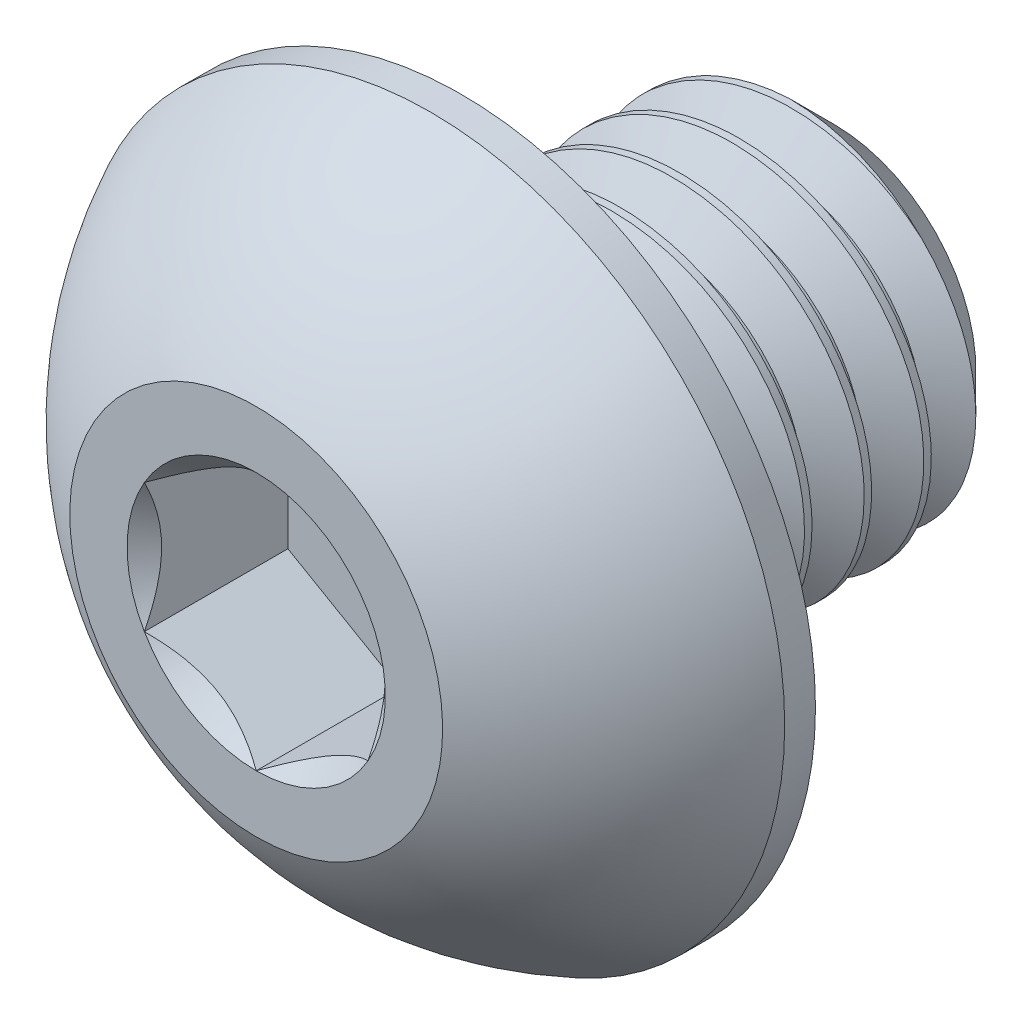
SolidWorks part; units mm, degrees
note: '?' marks a value the reader was unsure of.
ref_plane "Front" through (0, 0, 0) normal (0, 0, 1) x (1, 0, 0)
ref_plane "Top" through (0, 0, 0) normal (0, 1, 0) x (1, 0, 0)
ref_plane "Right" through (0, 0, 0) normal (1, 0, 0) x (0, 0, -1)
sketch "Sketch1" plane through (0, 0, 0) normal (1, 0, 0) x (0, 0, -1)
  line L2 (2.75, 2.5) -> (7.75, 2.5)
  line L3 (7.75, 2.5) -> (7.75, 0)
  line L4 (7.75, 0) -> (2.75, 0)
  line L6 (2.3375, 4.75) -> (2.75, 4.75) construction
  line L7 (7.75, 2.5) -> (7.75, -2.5) construction
  line L8 (0, 0) -> (2.75, 0) construction
  line L9 (2.75, 4.75) -> (2.75, -4.75) construction
  line L11 (2.75, 2.5) -> (2.75, 0)
  line L13 (0, 1.5) -> (0, -1.5) construction
  line L14 (0, 1.5) -> (0, 2.5) construction
  arc A3 (0, 2.5) -> (2.3375, 4.75) centre (4.6581, 0) cw construction
  dimension "D1" = 0.4125
revolve "Revolve1" add sketch "Sketch1" angle 360 mid plane about L4
sketch "Sketch3" plane through (0, 0, -7.75) normal (0, 0, -1) x (-1, 0, 0)
  circle A0 centre (0, 0) radius 2.5
curve "Helix/Spiral1" pitch 0.8 height 5.8 turns 7.25
chamfer "Chamfer1" distance 0.6 angle 45 1 edges at (0, 2.5, -7.75)
sketch "Sketch7" plane through (0, 0, 0) normal (1, 0, 0) x (0, 0, -1)
  line L6 (2.3375, 4.75) -> (2.75, 4.75) construction
  line L8 (0, 0) -> (2.75, 0) construction
  line L11 (2.75, 4.75) -> (2.75, -4.75) construction
  line L12 (2.3375, 4.75) -> (2.75, 4.75)
  line L13 (0, 0) -> (2.75, 0)
  line L14 (0, 1.5) -> (0, -1.5) construction
  line L15 (2.75, 4.75) -> (2.75, 0)
  line L16 (0, 2.5) -> (0, 0)
  arc A2 (2.3375, 4.75) -> (0, 2.5) centre (4.6581, 0) ccw construction
  arc A3 (2.3375, 4.75) -> (0, 2.5) centre (4.6581, 0) ccw
revolve "Revolve2" add sketch "Sketch7" angle 360 mid plane about L13
sketch "Sketch5" plane through (0, 0, 0) normal (0, 0, 1) x (1, 0, 0)
  line L1 (1.5, -0.866) -> (1.5, 0.866)
  line L2 (1.5, 0.866) -> (0, 1.7321)
  line L3 (0, 1.7321) -> (-1.5, 0.866)
  line L4 (-1.5, 0.866) -> (-1.5, -0.866)
  line L5 (-1.5, -0.866) -> (0, -1.7321)
  line L6 (0, -1.7321) -> (1.5, -0.866)
  circle A0 centre (0, 0) radius 1.5 construction
extrude "Cut-Extrude2" cut sketch "Sketch5" against normal blind 1.925
sketch "Sketch6" plane through (0, 0, 0) normal (0, 0, 1) x (1, 0, 0)
  circle A0 centre (0, 0) radius 1.7321
extrude "Cut-Extrude3" cut sketch "Sketch6" against normal blind 1.925 draft 45
sketch "Sketch2" plane through (0, 0, 0) normal (1, 0, 0) x (0, 0, -1)
  line L0 (7.15, 2.5) -> (7.85, 2.5)
  line L1 (7.85, 2.5) -> (7.55, 1.9804)
  line L2 (7.55, 1.9804) -> (7.45, 1.9804)
  line L3 (7.45, 1.9804) -> (7.15, 2.5)
  line L4 (7.3, 2.2402) -> (7.7, 2.2402) construction
  dimension "D1" = 60
  dimension "D2" = 0.1
  dimension "D3" = 0.4
sweep "Cut-Sweep1" cut profiles "Sketch2" path "Helix/Spiral1"
sketch "Sketch10" plane through (0, 0, 0) normal (1, 0, 0) x (0, 0, -1)
  line L0 (7.75, 2.5) -> (7.75, -2.5) construction
  point P0 (6.55, -2.5)
  dimension "D1" = 1.2
ref_axis "Center Axis 1" through (0, 0, -8.1113) along (0, 0, 1)?
ref_plane "Contact Plane 1" through (0, 0, -2.75) normal (0, 0, -1) x (-1, 0, 0)
ref_plane "Contact Plane 2" through (0, 0, 0) normal (0, 0, 1) x (1, 0, 0)
equation "\"D3@Helix/Spiral1\" = \"Lg@Sketch1\" + \"D4@Helix/Spiral1\""
equation "\"D2@Sketch2\" = \"D4@Helix/Spiral1\" * .125"
equation "\"D3@Sketch2\" = \"D4@Helix/Spiral1\" * .5"
equation "\"D1@Chamfer1\" = \"D4@Helix/Spiral1\" * .75"
equation "\"D1@Cut-Extrude2\" = \"Head Ht@Sketch1\" * .7"
equation "\"D1@Sketch1\" = \"Head Ht@Sketch1\" * .15"
equation "\"D1@Sketch10\" = \"D4@Helix/Spiral1\" * 1.5"
equation "\"D1@Cut-Extrude3\" = \"D1@Cut-Extrude2\""
